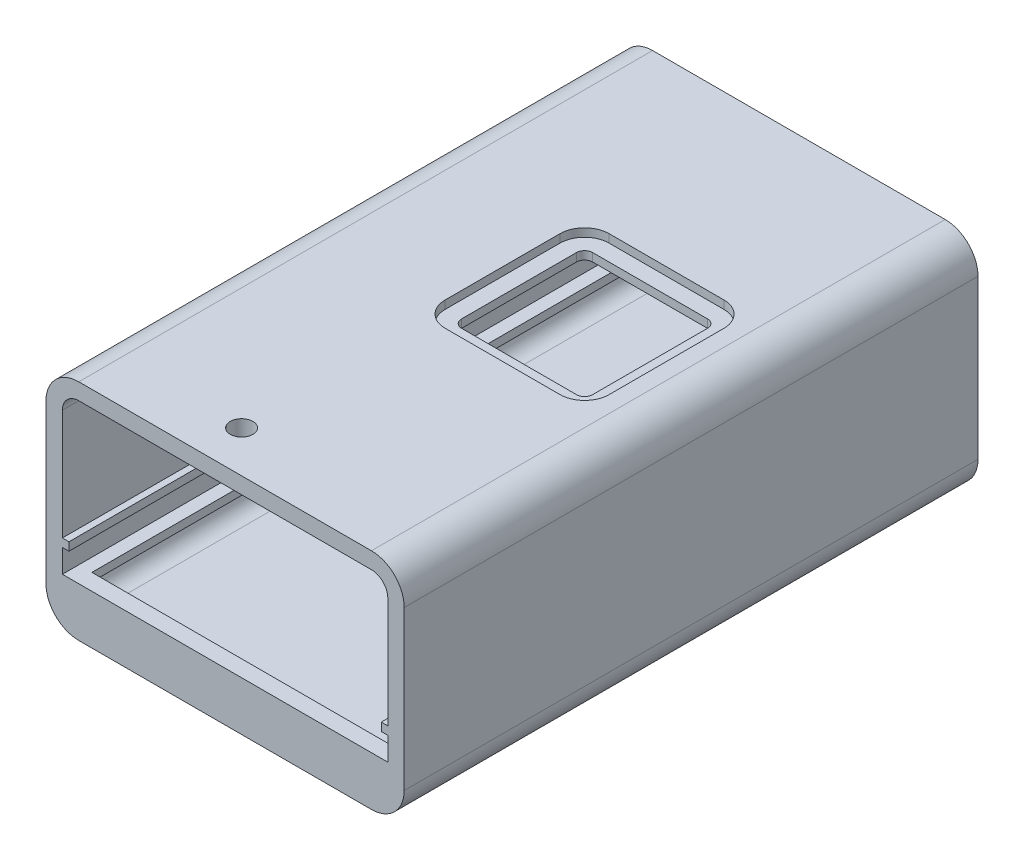
SolidWorks part; units mm, degrees
ref_plane "Front Plane" through (0, 0, 0) normal (0, 0, 1) x (1, 0, 0)
ref_plane "Top Plane" through (0, 0, 0) normal (0, 1, 0) x (1, 0, 0)
ref_plane "Right Plane" through (0, 0, 0) normal (1, 0, 0) x (0, 0, -1)
sketch "Sketch1" plane through (0, 0, 0) normal (0, 0, 1) x (1, 0, 0)
  line L0 (-34.8203, 16.2116) -> (-34.8203, 12.6116)
  line L1 (-35.8363, 16.2116) -> (14.5827, 16.2116)
  line L2 (-35.8363, 16.2116) -> (-35.8363, 12.6116)
  line L3 (-35.8363, 12.6116) -> (14.5827, 12.6116)
  line L4 (14.5827, 16.2116) -> (14.5827, 12.6116)
  line L5 (13.5667, 16.2116) -> (13.5667, 12.6116)
  line L6 (-35.8363, 12.6116) -> (-37.5927, 12.6116)
  line L7 (13.5667, 16.2116) -> (14.5827, 16.2116)
  line L8 (13.5667, 16.2116) -> (13.5667, 17.4816)
  line L9 (13.5667, 17.4816) -> (14.5827, 17.4816)
  line L10 (14.5827, 16.2116) -> (14.5827, 17.4816)
  line L11 (13.5667, 12.6116) -> (14.5827, 12.6116)
  line L13 (12.5507, 11.3416) -> (14.5827, 11.3416)
  line L14 (14.5827, 12.6116) -> (14.5827, 11.3416)
  line L15 (-35.8363, 16.2116) -> (-34.8203, 16.2116)
  line L16 (-35.8363, 16.2116) -> (-35.8363, 17.4816)
  line L17 (-35.8363, 17.4816) -> (-34.8203, 17.4816)
  line L18 (-34.8203, 16.2116) -> (-34.8203, 17.4816)
  line L19 (-35.8363, 12.6116) -> (-34.8203, 12.6116)
  line L20 (-35.8363, 12.6116) -> (-35.8363, 11.3416)
  line L21 (-35.8363, 11.3416) -> (-33.8043, 11.3416)
  line L23 (-35.8363, 12.6116) -> (14.5827, 12.6116)
  line L24 (-35.8363, 12.6116) -> (-35.8363, 10.0716)
  line L25 (-33.2963, 7.5316) -> (12.0427, 7.5316)
  line L26 (14.5827, 12.6116) -> (14.5827, 10.0716)
  line L27 (14.5827, 12.6116) -> (15.8105, 12.6116)
  line L28 (17.1227, 12.6116) -> (17.1227, 10.0716)
  line L29 (-35.8363, 16.2116) -> (14.5827, 16.2116)
  line L30 (-35.8363, 16.2116) -> (-35.8363, 34.6266)
  line L31 (-33.2963, 37.1666) -> (12.0427, 37.1666)
  line L32 (14.5827, 16.2116) -> (14.5827, 34.6266)
  line L33 (-33.2963, 4.9916) -> (12.0427, 4.9916)
  line L34 (-38.3763, 12.6116) -> (-38.3763, 10.0716)
  line L35 (-38.3763, 16.2116) -> (-38.3763, 12.6116)
  line L36 (-38.3763, 16.2116) -> (-38.3763, 34.6266)
  line L37 (-33.2963, 39.7066) -> (12.0427, 39.7066)
  line L38 (17.1227, 16.2116) -> (17.1227, 34.6266)
  line L39 (17.1227, 16.2116) -> (17.1227, 12.6116)
  line L40 (12.0427, 12.6116) -> (12.0427, 11.3416)
  line L41 (12.5507, 11.3416) -> (12.5507, 12.6116)
  line L42 (-33.8043, 11.3416) -> (-33.8043, 12.6116)
  arc A0 (12.0427, 7.5316) -> (14.5827, 10.0716) centre (12.0427, 10.0716) ccw
  arc A1 (-35.8363, 10.0716) -> (-33.2963, 7.5316) centre (-33.2963, 10.0716) ccw
  arc A2 (12.0427, 37.1666) -> (14.5827, 34.6266) centre (12.0427, 34.6266) cw
  arc A3 (-35.8363, 34.6266) -> (-33.2963, 37.1666) centre (-33.2963, 34.6266) cw
  arc A4 (12.0427, 4.9916) -> (17.1227, 10.0716) centre (12.0427, 10.0716) ccw
  arc A5 (-38.3763, 10.0716) -> (-33.2963, 4.9916) centre (-33.2963, 10.0716) ccw
  arc A6 (-38.3763, 34.6266) -> (-33.2963, 39.7066) centre (-33.2963, 34.6266) cw
  arc A7 (12.0427, 39.7066) -> (17.1227, 34.6266) centre (12.0427, 34.6266) cw
  point P4 (13.5667, 16.2116)
  point P5 (-34.8203, 16.2116)
  point P26 (-35.8363, 7.5316)
  point P33 (-35.8363, 37.1666)
  dimension "D10" = 2.54
  dimension "D12" = 2.54
  dimension "D1" = 50.419
  dimension "D2" = 3.6
  dimension "D3" = 1.016
  dimension "D4" = 1.016
  dimension "D5" = 1.27
  dimension "D6" = 1.27
  dimension "D7" = 1.27
  dimension "D8" = 1.27
  dimension "D9" = 5.08
  dimension "D11" = 20.955
  dimension "D14" = 2.032
  dimension "D13" = 2.54
extrude "Boss-Extrude1" add sketch "Sketch1" along normal blind 88.9 contours L3 L20 L21 | L1 L18 L17 L16 | A7 L37 A6 L36 L35 L34 A5 L33 A4 L28 L39 L38 L30 A3 L31 A2 L32 L10 L4 L14 L26 A0 L25 A1 L24 L20 L2 L16 | L1 L10 L9 L8 | L14 L3 L13 region at (-35.3283, 16.8466, 0) region at (-34.8203, 11.9766, 0) region at (14.0747, 16.8466, 0) region at (13.5667, 11.9766, 0) region at (16.4681, 11.3416, 0)
sketch "Sketch2" plane through (0, 12.6116, 0) normal (0, 1, 0) x (1, 0, 0)
  line L0 (14.5827, -88.9) -> (14.5827, 0) construction
  line L1 (-35.8363, -88.9) -> (14.5827, -88.9)
  line L2 (-35.8363, -88.9) -> (-35.8363, -86.36)
  line L3 (-35.8363, -86.36) -> (14.5827, -86.36)
  line L4 (14.5827, -88.9) -> (14.5827, -86.36)
  dimension "D1" = 2.54
extrude "Boss-Extrude2" add sketch "Sketch2" against normal blind 6.223
hole_wizard "Ø3.0mm Clearance Dowel Hole1" positions "Sketch5" profile "Sketch6" hole size "Ø3.0" standard "ANSI Metric" end condition through all
sketch "Sketch5" plane through (-44.5505, 37.1666, -20.9323) normal (0, -1, 0) x (-1, 0, 0)
  point P0 (-30.0502, -103.4061)
sketch "Sketch6" plane through (-14.5003, 37.1666, 82.4738) normal (1, 0, 0) x (0, 0, -1)
  line L0 (0, 0) -> (0, 2.54)
  line L1 (0, 2.54) -> (1.75, 2.54)
  line L2 (1.75, 2.54) -> (1.75, 0)
  line L5 (1.75, 0) -> (0, 0)
  line L11 (0, -6.35) -> (0, 107.95) construction
  dimension "Thru Hole Dia." = 3.5
  dimension "Thru Hole Depth" = 2.54
sketch "Sketch7" plane through (0, 39.7066, 0) normal (0, 1, 0) x (1, 0, 0)
  line L0 (-33.2963, 0) -> (12.0427, 0) construction
  line L1 (5.6927, -27.94) -> (-12.0873, -27.94)
  line L2 (9.5027, -31.75) -> (9.5027, -49.53)
  line L3 (5.6927, -53.34) -> (-12.0873, -53.34)
  line L4 (-15.8973, -31.75) -> (-15.8973, -49.53)
  line L5 (12.0427, -88.9) -> (12.0427, 0) construction
  line L6 (6.9627, -31.75) -> (6.9627, -49.53)
  line L7 (5.6927, -50.8) -> (-12.0873, -50.8)
  line L8 (-13.3573, -31.75) -> (-13.3573, -49.53)
  line L9 (5.6927, -30.48) -> (-12.0873, -30.48)
  arc A0 (-12.0873, -27.94) -> (-15.8973, -31.75) centre (-12.0873, -31.75) ccw
  arc A1 (-12.0873, -53.34) -> (-15.8973, -49.53) centre (-12.0873, -49.53) cw
  arc A2 (9.5027, -49.53) -> (5.6927, -53.34) centre (5.6927, -49.53) cw
  arc A3 (5.6927, -27.94) -> (9.5027, -31.75) centre (5.6927, -31.75) cw
  arc A4 (6.9627, -49.53) -> (5.6927, -50.8) centre (5.6927, -49.53) cw
  arc A5 (-12.0873, -50.8) -> (-13.3573, -49.53) centre (-12.0873, -49.53) cw
  arc A6 (-12.0873, -30.48) -> (-13.3573, -31.75) centre (-12.0873, -31.75) ccw
  arc A7 (5.6927, -30.48) -> (6.9627, -31.75) centre (5.6927, -31.75) cw
  point P10 (-15.8973, -27.94)
  point P15 (9.5027, -53.34)
  point P18 (9.5027, -27.94)
  dimension "D5" = 3.81
  dimension "D1" = 25.4
  dimension "D2" = 25.4
  dimension "D3" = 27.94
  dimension "D4" = 2.54
  dimension "D6" = 2.54
extrude "Cut-Extrude1" cut sketch "Sketch7" against normal blind 7.62 contours L6 A4 L7 A5 L8 A6 L9 A7
extrude "Cut-Extrude2" cut sketch "Sketch7<3>" against normal blind 1.27
sketch "Sketch7<3>" plane through (0, 39.7066, 0) normal (0, 1, 0) x (1, 0, 0) same geometry as "Sketch7"
